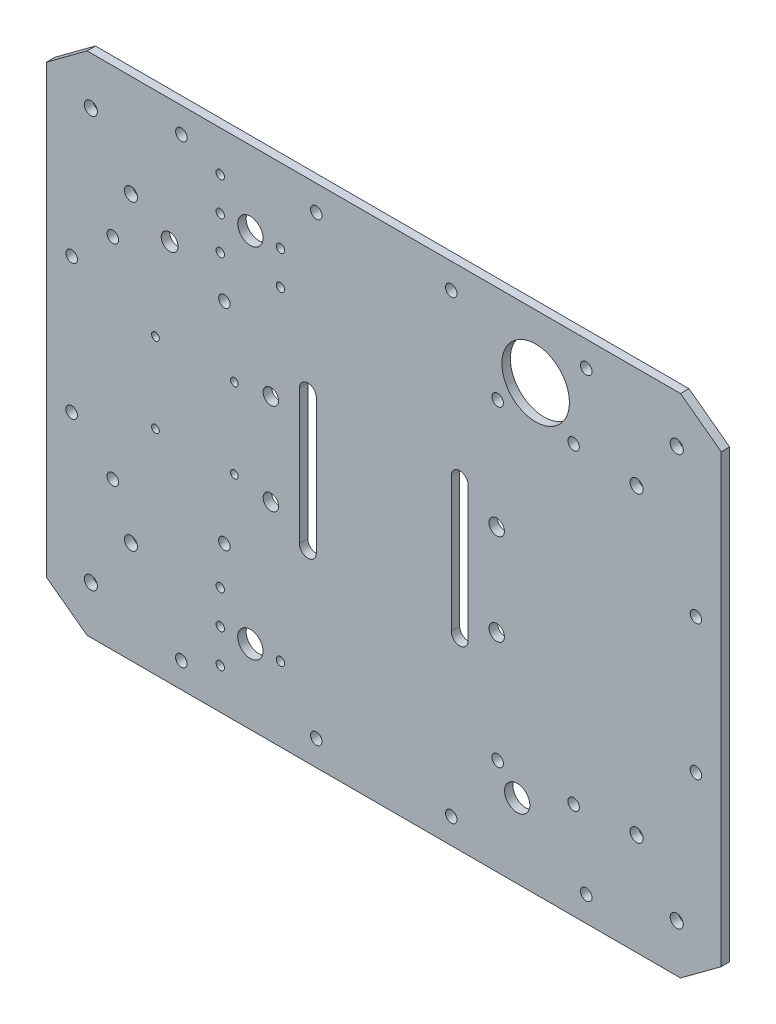
SolidWorks part; units mm, degrees
material "Thornel Mat VMA"
ref_plane "Front Plane" through (0, 0, 0) normal (0, 0, 1) x (1, 0, 0)
ref_plane "Top Plane" through (0, 0, 0) normal (0, 1, 0) x (1, 0, 0)
ref_plane "Right Plane" through (0, 0, 0) normal (1, 0, 0) x (0, 0, -1)
sketch "Sketch1" plane through (0, 0, 0) normal (0, 0, 1) x (1, 0, 0)
  line L0 (-127, 0) -> (127, 0) construction
  line L1 (0, -95.25) -> (0, 95.25) construction
  line L2 (-107.95, 0) -> (-107.95, 41.011) construction
  line L3 (-107.95, 41.011) -> (-95.25, 41.011) construction
  line L4 (-95.25, 41.011) -> (-79.9365, 52.3423) construction
  line L5 (-79.9365, 52.3423) -> (-79.9365, 76.2) construction
  line L6 (-79.9365, 76.2) -> (0, 76.2) construction
  line L7 (-95.25, 41.011) -> (-127, 83.9186) construction
  line L8 (-79.9365, 52.3423) -> (-111.6865, 95.25) construction
  line L9 (-111.6865, -95.25) -> (-127, -83.9186)
  line L10 (111.6865, -95.25) -> (127, -83.9186)
  line L11 (111.6865, 95.25) -> (127, 83.9186)
  line L12 (-87.5933, 46.6767) -> (-95.1475, 56.8856) construction
  line L13 (-95.1475, 56.8856) -> (-110.256, 77.3036) construction
  line L24 (127, -83.9186) -> (127, 83.9186)
  line L26 (111.6865, 95.25) -> (-111.6865, 95.25)
  line L27 (-111.6865, 95.25) -> (-127, 83.9186)
  line L28 (-127, 83.9186) -> (-127, -83.9186)
  line L30 (-111.6865, -95.25) -> (111.6865, -95.25)
  circle A0 centre (-95.1475, 56.8856) radius 2.4638
  circle A1 centre (-110.256, 77.3036) radius 2.4638
  circle A2 centre (110.256, 77.3036) radius 2.4638
  circle A3 centre (95.1475, 56.8856) radius 2.4638
  circle A4 centre (-110.256, -77.3036) radius 2.4638
  circle A5 centre (-95.1475, -56.8856) radius 2.4638
  circle A6 centre (110.256, -77.3036) radius 2.4638
  circle A7 centre (95.1475, -56.8856) radius 2.4638
  point P12 (0, 0)
  dimension "D1" = 190.5
  dimension "D2" = 254
  dimension "D3" = 19.05
  dimension "D4" = 19.05
  dimension "D5" = 12.7
  dimension "D6" = 19.05
  dimension "D7" = 143.5
  dimension "D8" = 12.7
  dimension "D9" = 25.4
extrude "Boss-Extrude1" add sketch "Sketch1" along normal blind 3.175
sketch "Sketch2" plane through (0, 0, 3.175) normal (0, 0, 1) x (1, 0, 0)
  line L0 (-127, 0) -> (127, 0) construction
  line L1 (-127, 83.9186) -> (-127, -83.9186) construction
  line L2 (127, -83.9186) -> (127, 83.9186) construction
  line L3 (57.15, 65.0875) -> (57.15, -65.0875) construction
  line L4 (38.1, 65.0875) -> (76.2, 65.0875)
  line L5 (38.1, 65.0875) -> (38.1, -65.0875)
  line L6 (38.1, -65.0875) -> (76.2, -65.0875)
  line L7 (76.2, 65.0875) -> (76.2, -65.0875)
  line L8 (38.1, 65.0875) -> (76.2, -65.0875) construction
  line L9 (38.1, -65.0875) -> (76.2, 65.0875) construction
  line L10 (57.15, 58.7375) -> (47.625, 58.7375) construction
  line L11 (47.625, 58.7375) -> (38.1, 58.7375) construction
  circle A0 centre (42.8625, 58.7375) radius 2.159
  circle A1 centre (42.8625, -58.7375) radius 2.159
  circle A2 centre (71.4375, -58.7375) radius 2.159
  circle A3 centre (71.4375, 58.7375) radius 2.159
  point P6 (57.15, 0)
  point P17 (42.8625, 58.7375)
  dimension "D1" = 38.1
  dimension "D2" = 130.175
  dimension "D3" = 6.35
  dimension "D4" = 9.525
  dimension "D5" = 69.85
extrude "Cut-Extrude1" cut sketch "Sketch2" against normal through all contours A1 | A2 | A3 | A0 region at (42.8625, 58.7375, 3.175) region at (42.8625, -58.7375, 3.175) region at (71.4375, -58.7375, 3.175) region at (71.4375, 58.7375, 3.175)
sketch "Sketch3" plane through (0, 0, 3.175) normal (0, 0, 1) x (1, 0, 0)
  line L0 (0, 95.25) -> (0, -95.25) construction
  line L1 (111.6865, 95.25) -> (-111.6865, 95.25) construction
  line L2 (-111.6865, -95.25) -> (111.6865, -95.25) construction
  line L3 (127, 0) -> (-127, 0) construction
  line L4 (127, -83.9186) -> (127, 83.9186) construction
  line L5 (-127, 83.9186) -> (-127, -83.9186) construction
  line L8 (119.3433, -89.5843) -> (111.789, -79.3753) construction
  line L10 (111.6865, -95.25) -> (127, -83.9186) construction
  line L11 (111.6865, -95.25) -> (127, -83.9186)
  circle A0 centre (111.789, -79.3753) radius 1.9844
  circle A1 centre (96.6805, -58.9574) radius 1.9844
  dimension "D2" = 3.9688
  dimension "D3" = 3.9688
  dimension "D1" = 12.7
  dimension "D4" = 25.4
sketch "Sketch5" plane through (0, 0, 0) normal (0, 0, -1) x (-1, 0, 0)
  line L0 (-127, 0) -> (127, 0) construction
  line L1 (105.9946, 43.5) -> (55.9947, 43.5) construction
  line L2 (105.9946, 43.5) -> (105.9946, -43.5) construction
  line L3 (105.9946, -43.5) -> (55.9947, -43.5) construction
  line L4 (55.9947, 43.5) -> (55.9947, -43.5) construction
  line L5 (89.2369, 18.0341) -> (89.2369, -18.0339)
  line L6 (67.8946, 95.25) -> (67.8946, -95.25) construction
  line L7 (-71.4375, 58.7375) -> (-42.8625, 58.7375) construction
  line L8 (0, 64.0679) -> (0, -49.8393) construction
  line L9 (-42.5, 17.2) -> (42.5, 17.2) construction
  line L10 (-42.5, 17.2) -> (-42.5, -17.2) construction
  line L11 (-42.5, -17.2) -> (42.5, -17.2) construction
  line L12 (42.5, 17.2) -> (42.5, -17.2) construction
  line L13 (-42.5, 17.2) -> (42.5, -17.2) construction
  line L14 (-42.5, -17.2) -> (42.5, 17.2) construction
  line L15 (80.5946, 60.96) -> (31.75, 60.96) construction
  line L16 (61.5446, -67.31) -> (-87.4336, -67.31) construction
  line L17 (50.2154, -67.31) -> (50.2154, 67.31) construction
  line L18 (50.2154, 67.31) -> (38.8861, 67.31) construction
  line L19 (-28.575, 25.4) -> (-28.575, -25.4) construction
  line L21 (-127, -83.9186) -> (-127, 83.9186) construction
  line L22 (-57.15, 71.4375) -> (80.5946, 71.4375) construction
  line L23 (80.5946, 71.4375) -> (80.5946, 48.58) construction
  line L25 (80.5946, -77.0458) -> (80.5946, 48.58) construction
  line L26 (127, 0) -> (-127, 0) construction
  line L27 (80.9947, 0) -> (80.9947, -8419.0368) construction
  line L28 (-25.4, 25.4) -> (-25.4, -25.4)
  line L29 (-31.75, 25.4) -> (-31.75, -25.4)
  line L30 (28.575, 25.4) -> (28.575, -25.4) construction
  line L31 (25.4, 25.4) -> (25.4, -25.4)
  line L32 (31.75, 25.4) -> (31.75, -25.4)
  line L33 (71.0787, 0) -> (71.0787, 12.3782) construction
  line L34 (53.2197, 18.0341) -> (89.2369, 18.0341)
  line L35 (53.2197, 18.0341) -> (53.2197, -18.0339)
  line L36 (53.2197, -18.0339) -> (89.2369, -18.0339)
  line L40 (-57.15, 58.7375) -> (-57.15, 95.25) construction
  circle A0 centre (61.5446, -54.61) radius 1.5875
  circle A1 centre (61.5446, -67.31) radius 1.5875
  circle A2 centre (80.5946, 48.58) radius 3.175
  circle A3 centre (-57.15, 71.4375) radius 12.7
  circle A4 centre (61.5446, 54.61) radius 1.5875
  circle A5 centre (61.5446, -80.01) radius 1.5875
  circle A6 centre (-50.2154, -67.31) radius 4.7625
  circle A7 centre (50.2154, -67.31) radius 4.7625
  circle A8 centre (61.5446, 67.31) radius 1.5875
  circle A9 centre (61.5446, 80.01) radius 1.5875
  circle A10 centre (50.2154, 67.31) radius 4.7625
  circle A12 centre (59.9952, 39.4995) radius 2.159
  circle A13 centre (101.9941, 39.4995) radius 2.159
  circle A14 centre (59.9952, -39.4995) radius 2.159
  circle A15 centre (101.9941, -39.4995) radius 2.159
  circle A16 centre (38.8861, 67.31) radius 1.5875
  circle A17 centre (38.8861, 54.61) radius 1.5875
  circle A18 centre (38.8861, -67.31) radius 1.5875
  circle A19 centre (38.8861, -54.61) radius 1.5875
  arc A20 (-25.4, 25.4) -> (-31.75, 25.4) centre (-28.575, 25.4) ccw
  arc A21 (-31.75, -25.4) -> (-25.4, -25.4) centre (-28.575, -25.4) ccw
  arc A22 (25.4, 25.4) -> (31.75, 25.4) centre (28.575, 25.4) cw
  arc A23 (31.75, -25.4) -> (25.4, -25.4) centre (28.575, -25.4) cw
  circle A24 centre (56.2197, 15.0341) radius 1.4478
  circle A25 centre (56.2197, -15.0341) radius 1.4478
  circle A26 centre (85.9377, -15.0341) radius 1.4478
  circle A27 centre (85.9377, 15.0341) radius 1.4478
  circle A28 centre (-42.5, 17.2) radius 2.9083
  circle A29 centre (-42.5, -17.2) radius 2.9083
  circle A30 centre (42.5, -17.2) radius 2.9083
  circle A31 centre (42.5, 17.2) radius 2.9083
  point P0 (80.9947, 0)
  point P9 (0, 0)
  point P77 (-28.575, 0)
  point P84 (28.575, 0)
  point P89 (71.0787, 0)
  dimension "D10" = 6.35
  dimension "D15" = 2.9997
  dimension "D25" = 4.0005
  dimension "D45" = 2.8956
  dimension "D13" = 14.859
  dimension "D14" = 3
  dimension "D8" = 111.76
  dimension "D1" = 87.0001
  dimension "D2" = 49.9999
  dimension "D4" = 34.4
  dimension "D5" = 85
  dimension "D6" = 6.35
  dimension "D7" = 12.7
  dimension "D11" = 5.08
  dimension "D12" = 25.4
  dimension "D26" = 4.0005
  dimension "D38" = 50.8
  dimension "D39" = 6.35
  dimension "D40" = 28.575
  dimension "D41" = 36.0172
  dimension "D42" = 36.068
  dimension "D44" = 3
extrude "Cut-Extrude2" cut sketch "Sketch5" against normal through all contours A3 | A2 | A14 | A15 | A13 | A12 | L29 A21 L28 A20 | A23 L4 A22 L31 | A23 L32 A22 L4 | A27 | A24 | A25 | A26
sketch "Sketch6" plane through (0, 0, 0) normal (0, 0, -1) x (-1, 0, 0)
  line L0 (0, 0) -> (-135.1326, 0) construction
  line L1 (0, 0) -> (0, -95.25) construction
  line L2 (111.6865, -95.25) -> (-111.6865, -95.25) construction
  line L3 (-76.2, -95.25) -> (-76.2, -85.725) construction
  line L4 (117.475, 0) -> (117.475, -25.4) construction
  line L5 (127, 0) -> (-127, 0) construction
  line L6 (127, 83.9186) -> (127, -83.9186) construction
  circle A0 centre (-76.2, -85.725) radius 2.159
  circle A1 centre (-25.4, -85.725) radius 2.159
  circle A2 centre (25.4, -85.725) radius 2.159
  circle A3 centre (76.2, -85.725) radius 2.159
  circle A4 centre (76.2, 85.725) radius 2.159
  circle A5 centre (25.4, 85.725) radius 2.159
  circle A6 centre (-25.4, 85.725) radius 2.159
  circle A7 centre (-76.2, 85.725) radius 2.159
  circle A8 centre (117.475, -25.4) radius 2.159
  circle A9 centre (117.475, 25.4) radius 2.159
  circle A10 centre (-117.475, 25.4) radius 2.159
  circle A11 centre (-117.475, -25.4) radius 2.159
  dimension "D2" = 9.525
  dimension "D3" = 76.2
  dimension "D5" = 9.525
  dimension "D6" = 25.4
  dimension "D4" = 4
extrude "Cut-Extrude3" cut sketch "Sketch6" against normal through all
extrude "Cut-Extrude4" cut sketch "Sketch5<3>" against normal through all contours A28 | A29 | A31 | A30
sketch "Sketch5<3>" plane through (0, 0, 0) normal (0, 0, -1) x (-1, 0, 0) same geometry as "Sketch5"
sketch "Sketch7" plane through (0, 0, 3.175) normal (0, 0, 1) x (1, 0, 0)
extrude "Cut-Extrude5" cut sketch "Sketch5<4>" against normal through all contours A10 | A9 | A8 | A4 | A0 | A1 | A5 | A7 | A6
sketch "Sketch5<4>" plane through (0, 0, 0) normal (0, 0, -1) x (-1, 0, 0) same geometry as "Sketch5"
extrude "Cut-Extrude6" cut sketch "Sketch5<5>" against normal blind 2.54 contours A18 | A17 | A16
sketch "Sketch5<5>" plane through (0, 0, 0) normal (0, 0, -1) x (-1, 0, 0) same geometry as "Sketch5"
extrude "Cut-Extrude7" cut sketch "Sketch5<6>" against normal through all contours A17 | A18 | A16
sketch "Sketch5<6>" plane through (0, 0, 0) normal (0, 0, -1) x (-1, 0, 0) same geometry as "Sketch5"
